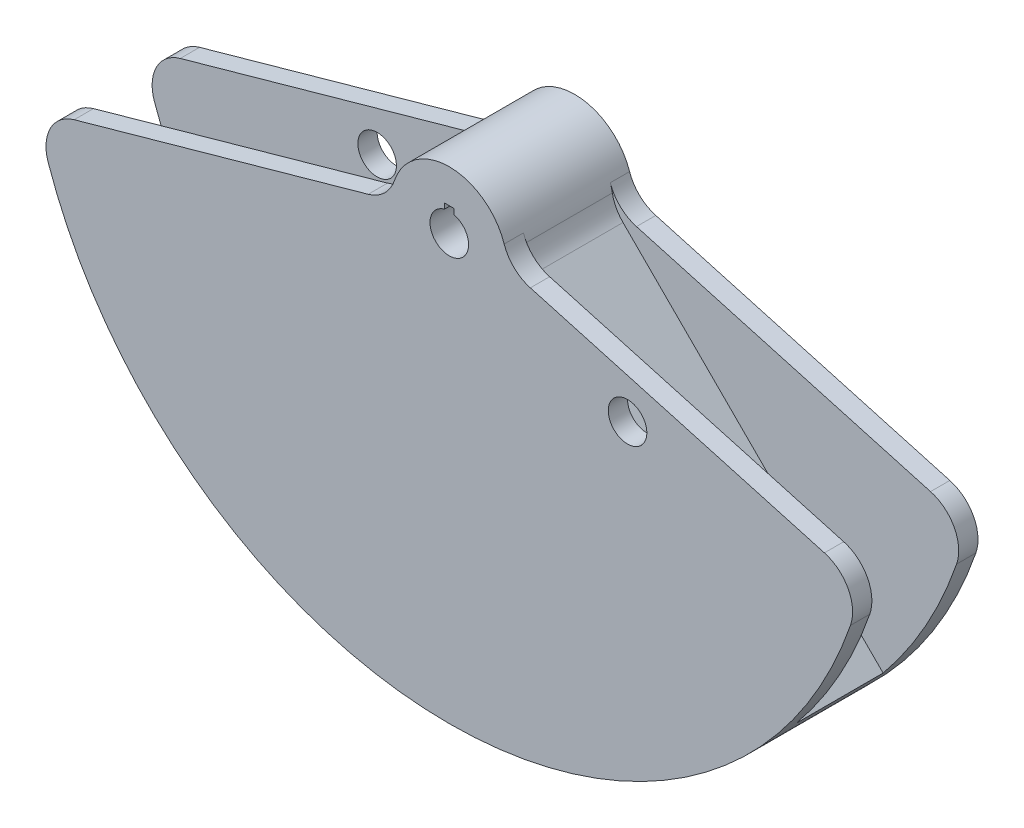
SolidWorks part; units mm, degrees
material "AISI 1020"
ref_plane "Front Plane" through (0, 0, 0) normal (0, 0, 1) x (1, 0, 0)
ref_plane "Top Plane" through (0, 0, 0) normal (0, 1, 0) x (1, 0, 0)
ref_plane "Right Plane" through (0, 0, 0) normal (1, 0, 0) x (0, 0, -1)
other "Center of Mass"
sketch "Sketch1" plane through (0, 0, 0) normal (0, 0, 1) x (1, 0, 0)
  line L0 (-215.6951, -177.5951) -> (-44.4734, -6.3734)
  line L1 (-38.1, 0) -> (38.1, 0) construction
  line L2 (44.4734, -6.3734) -> (215.6951, -177.5951)
  line L3 (0, 0) -> (-117.3327, -48.6008) construction
  line L4 (0, 0) -> (0, -279.4) construction
  line L5 (117.3327, -48.6008) -> (0, 0) construction
  arc A0 (-215.6951, -177.5951) -> (215.6951, -177.5951) centre (0, 0) ccw
  circle A1 centre (0, 0) radius 127 construction
  circle A2 centre (0, 0) radius 12.7
  arc A3 (37.4603, 6.9523) -> (-37.4603, 6.9523) centre (0, 0) ccw
  circle A4 centre (-117.3327, -48.6008) radius 12.7 construction
  circle A5 centre (117.3327, -48.6008) radius 12.7 construction
  arc A6 (44.4734, -6.3734) -> (37.4603, 6.9523) centre (62.4339, 11.5872) cw
  arc A7 (-44.4734, -6.3734) -> (-37.4603, 6.9523) centre (-62.4339, 11.5872) ccw
  dimension "D1" = 558.8
  dimension "D2" = 254
  dimension "D3" = 25.4
  dimension "D4" = 25.4
  dimension "D5" = 25.4
  dimension "D8" = 25.4
  dimension "D6" = 135
  dimension "D7" = 67.5
  dimension "D9" = 90
extrude "Boss-Extrude1" add sketch "Sketch1" along normal mid plane 57.15
sketch "Sketch5" plane through (0, 0, 28.575) normal (0, 0, 1) x (1, 0, 0)
  line L0 (-246.9092, -58.5606) -> (-53.3494, -4.2767)
  line L1 (-38.1, 0) -> (38.1, 0) construction
  line L2 (53.3494, -4.2767) -> (246.9092, -58.5606)
  line L3 (0, 0) -> (-117.3327, -48.6008) construction
  line L4 (0, 0) -> (0, -279.4) construction
  line L5 (117.3327, -48.6008) -> (0, 0) construction
  arc A0 (-264.0554, -91.3187) -> (264.0554, -91.3187) centre (0, 0) ccw
  circle A1 centre (0, 0) radius 127 construction
  circle A2 centre (0, 0) radius 12.7
  arc A3 (36.1249, 12.1078) -> (-36.1249, 12.1078) centre (0, 0) ccw
  circle A4 centre (-117.3327, -48.6008) radius 12.7 construction
  circle A5 centre (117.3327, -48.6008) radius 12.7
  arc A6 (53.3494, -4.2767) -> (36.1249, 12.1078) centre (60.2082, 20.1797) cw
  arc A7 (-53.3494, -4.2767) -> (-36.1249, 12.1078) centre (-60.2082, 20.1797) ccw
  arc A8 (-246.9092, -58.5606) -> (-264.0554, -91.3187) centre (-240.0504, -83.017) ccw
  arc A9 (246.9092, -58.5606) -> (264.0554, -91.3187) centre (240.0504, -83.017) cw
  dimension "D1" = 558.8
  dimension "D2" = 254
  dimension "D3" = 25.4
  dimension "D5" = 25.4
  dimension "D8" = 25.4
  dimension "D4" = 25.4
  dimension "D10" = 25.4
  dimension "D6" = 135
  dimension "D7" = 67.5
  dimension "D9" = 25.4
extrude "Boss-Extrude2" add sketch "Sketch5" along normal blind 12.7
sketch "Sketch6" plane through (0, 0, -28.575) normal (0, 0, -1) x (-1, 0, 0)
  line L0 (-246.9092, -58.5606) -> (-53.3494, -4.2767)
  line L1 (-38.1, 0) -> (38.1, 0) construction
  line L2 (53.3494, -4.2767) -> (246.9092, -58.5606)
  line L3 (0, 0) -> (-117.3327, -48.6008) construction
  line L4 (0, 0) -> (0, -279.4) construction
  line L5 (117.3327, -48.6008) -> (0, 0) construction
  arc A0 (-264.0554, -91.3187) -> (264.0554, -91.3187) centre (0, 0) ccw
  circle A1 centre (0, 0) radius 127 construction
  circle A2 centre (0, 0) radius 12.7
  arc A3 (36.1249, 12.1078) -> (-36.1249, 12.1078) centre (0, 0) ccw
  circle A4 centre (-117.3327, -48.6008) radius 12.7 construction
  circle A5 centre (117.3327, -48.6008) radius 12.7
  arc A6 (53.3494, -4.2767) -> (36.1249, 12.1078) centre (60.2082, 20.1797) cw
  arc A7 (-53.3494, -4.2767) -> (-36.1249, 12.1078) centre (-60.2082, 20.1797) ccw
  arc A8 (246.9092, -58.5606) -> (264.0554, -91.3187) centre (240.0504, -83.017) cw
  arc A9 (-246.9092, -58.5606) -> (-264.0554, -91.3187) centre (-240.0504, -83.017) ccw
  dimension "D1" = 558.8
  dimension "D2" = 254
  dimension "D3" = 25.4
  dimension "D4" = 25.4
  dimension "D7" = 25.4
  dimension "D9" = 25.4
  dimension "D10" = 25.4
  dimension "D5" = 135
  dimension "D6" = 67.5
  dimension "D8" = 25.4
extrude "Boss-Extrude4" add sketch "Sketch6" along normal blind 12.7
sketch "Sketch8" plane through (0, 0, 0) normal (0, 0, 1) x (1, 0, 0)
  line L0 (0, 0) -> (0, 12.7) construction
  line L2 (3.175, 9.525) -> (-3.175, 9.525)
  line L3 (3.175, 9.525) -> (3.175, 15.875)
  line L4 (3.175, 15.875) -> (-3.175, 15.875)
  line L5 (-3.175, 9.525) -> (-3.175, 15.875)
  line L6 (3.175, 9.525) -> (-3.175, 15.875) construction
  line L7 (3.175, 15.875) -> (-3.175, 9.525) construction
  circle A0 centre (0, 0) radius 12.7 construction
  arc A1 (3.175, 12.2967) -> (-3.175, 12.2967) centre (0, 0) ccw
  dimension "D1" = 6.35
  dimension "D2" = 6.35
extrude "Cut-Extrude1" cut sketch "Sketch8" against normal through all both and the other way through all contours L3 L4 L5 L2
